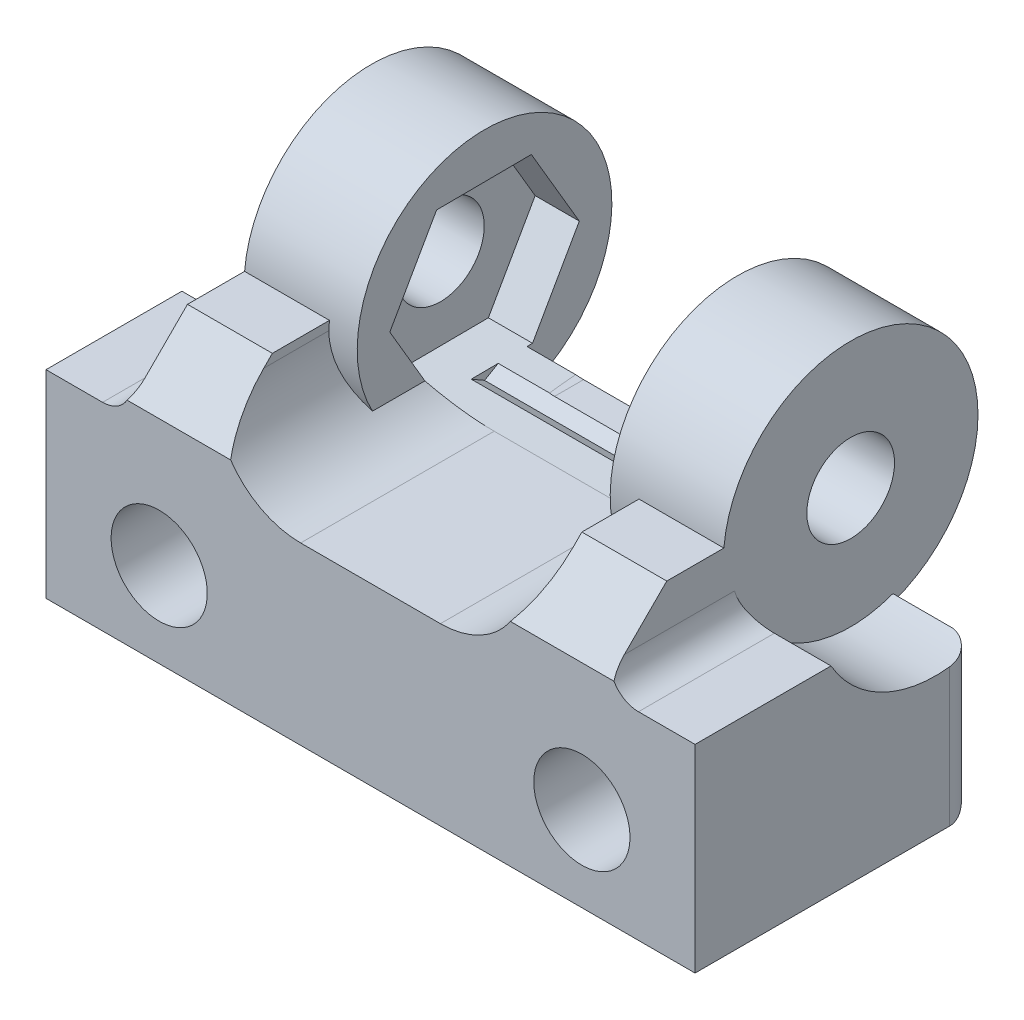
SolidWorks part; units mm, degrees
ref_plane "Спереди" through (0, 0, 0) normal (0, 0, 1) x (1, 0, 0)
ref_plane "Сверху" through (0, 0, 0) normal (0, 1, 0) x (1, 0, 0)
ref_plane "Справа" through (0, 0, 0) normal (1, 0, 0) x (0, 0, -1)
sketch "Эскиз1" plane through (0, 0, 0) normal (0, 0, 1) x (1, 0, 0)
  line L1 (-15, 4) -> (15, 4)
  line L2 (-15, 4) -> (-15, -4)
  line L3 (-15, -4) -> (15, -4)
  line L4 (15, 4) -> (15, -4)
  line L5 (-15, 4) -> (15, -4) construction
  line L6 (-15, -4) -> (15, 4) construction
  point P0 (0, 0)
  dimension "D1" = 30
  dimension "D2" = 8
extrude "Бобышка-Вытянуть1" add sketch "Эскиз1" along normal blind 5
sketch "Эскиз2" plane through (0, 0, 5) normal (0, 0, 1) x (1, 0, 0)
  line L0 (15, 4) -> (10.58, 4)
  line L1 (15, 4) -> (-15, 4) construction
  line L2 (10.58, 4) -> (-3.52, 4)
  line L3 (-3.52, 4) -> (-7.94, 4)
  line L4 (-7.94, 4) -> (-15, 4)
  line L5 (-15, 4) -> (-15, -4)
  line L6 (-15, 4) -> (-15, -4) construction
  line L7 (-15, -4) -> (-7.94, -4)
  line L8 (-15, -4) -> (15, -4) construction
  line L9 (-7.94, -4) -> (-7.94, 4)
  line M5 (15, 4) -> (-15, 4)
  line M6 (-15, 4) -> (-15, -4)
  line M7 (-15, -4) -> (15, -4)
  dimension "D1" = 4.42
  dimension "D2" = 14.1
  dimension "D3" = 4.42
extrude "Вырез-Вытянуть4" cut sketch "Эскиз2" against normal through all contours L9 M7 M5 M6 region at (-11.47, 0, 5)
sketch "Эскиз9" plane through (0, 0, 5) normal (0, 0, 1) x (1, 0, 0)
  line L0 (15, -4) -> (15, -1)
  line L1 (15, -4) -> (15, 4) construction
  line L2 (15, -1) -> (11, -1)
  line L3 (3.53, 4) -> (3.53, -4)
  line L4 (15, 4) -> (-7.94, 4) construction
  line L5 (-7.94, -4) -> (15, -4) construction
  circle A0 centre (11, -1) radius 1.5
  circle A1 centre (-3.94, -1) radius 1.5
  dimension "D3" = 3
  dimension "D1" = 3
  dimension "D2" = 4
extrude "Вырез-Вытянуть5" cut sketch "Эскиз9" against normal through all contours A1 | A0 region at (9.5424, -1, 5) region at (-3.94, -1, 5)
sketch "Эскиз10" plane through (0, 4, 0) normal (0, 1, 0) x (1, 0, 0)
  line L1 (-7.94, 0) -> (15, 0)
  line L2 (-7.94, 0) -> (-7.94, -5)
  line L3 (-7.94, -5) -> (15, -5)
  line L4 (15, 0) -> (15, -5)
extrude "Бобышка-Вытянуть2" add sketch "Эскиз10" along normal blind 4
sketch "Эскиз12" plane through (0, 0, 5) normal (0, 0, 1) x (1, 0, 0)
  line L0 (15, 8) -> (9, 8)
  line L1 (-7.94, 8) -> (15, 8) construction
  line L2 (9, 8) -> (-1.94, 8)
  line L3 (-1.94, 8) -> (-7.94, 8)
  line L4 (-1.94, 8) -> (-1.94, 2.1953)
  line L5 (-1.94, 2.1953) -> (9, 2.1953)
  line L6 (9, 2.1953) -> (9, 8)
  line M8 (15, 8) -> (-7.94, 8)
  dimension "D1" = 6
extrude "Вырез-Вытянуть6" cut sketch "Эскиз12" against normal through all contours L5 L6 L4 M8 region at (3.53, 5.0977, 5)
sketch "Эскиз14" plane through (9, 0, 0) normal (-1, 0, 0) x (0, 0, 1)
  line L0 (0, 8) -> (5, 2.1953)
  line L1 (5, 2.1953) -> (5, 8)
  line L2 (5, 8) -> (0, 2.1953)
  circle A0 centre (2.5, 5.0977) radius 1
  dimension "D1" = 2
extrude "Вырез-Вытянуть7" cut sketch "Эскиз14" against normal through all and the other way through all contours L0 A0 L2 | L0 A0 L2 | L2 A0 L0 | L2 A0 L0 region at (9, 5.7096, 2.5) region at (9, 5.0977, 1.9125) region at (9, 5.0977, 3.0875) region at (9, 4.4858, 2.5)
sketch "Эскиз15" plane through (9, 0, 0) normal (-1, 0, 0) x (0, 0, 1)
  line L1 (2.5, 2.7305) -> (4.55, 3.9141)
  line L2 (4.55, 3.9141) -> (4.55, 6.2812)
  line L3 (4.55, 6.2812) -> (2.5, 7.4648)
  line L4 (2.5, 7.4648) -> (0.45, 6.2812)
  line L5 (0.45, 6.2812) -> (0.45, 3.9141)
  line L6 (0.45, 3.9141) -> (2.5, 2.7305)
  circle A0 centre (2.5, 5.0977) radius 1
  circle A1 centre (2.5, 5.0977) radius 2.05 construction
  dimension "D1" = 4.1
extrude "Вырез-Вытянуть8" cut sketch "Эскиз15" against normal blind 1.7 and the other way blind 12.7
fillet "Скругление3" radius 3 2 edges at (-1.94, 2.1953, 2.5) (9, 2.1953, 2.5)
sketch "Эскиз17" plane through (15, 0, 0) normal (1, 0, 0) x (0, 0, -1)
  line L0 (-5, 8) -> (0, 8)
  line L1 (0, 8) -> (0, 3)
  line L2 (0, -4) -> (0, 8) construction
  line L3 (-5, 3) -> (-5, 8)
  line L4 (-5, -4) -> (-5, 8) construction
  line L5 (-5, 8) -> (-5.0493, 7.8026)
  line L6 (-4, 2) -> (-1, 2)
  arc A0 (-5, 3) -> (-4, 2) centre (-4, 3) ccw
  arc A1 (-1, 2) -> (0, 3) centre (-1, 3) ccw
  point P13 (-5, 2)
  point P16 (0, 2)
  circle M3 centre (-2.5, 5.0977) radius 1
  line M4 (0, -4) -> (0, 8)
  line M5 (0, 8) -> (-5, 8)
  line M6 (-5, 8) -> (-5, -4)
  dimension "D2" = 1
  dimension "D3" = 1
  dimension "D1" = 6
extrude "Вырез-Вытянуть10" cut sketch "Эскиз17" against normal blind 3 contours L6 A1 A0 M4 M5 M6 M3 region at (15, 7.9219, 2.5)
sketch "Эскиз18" plane through (-7.94, 0, 0) normal (-1, 0, 0) x (0, 0, 1)
  line L0 (0, 8) -> (5, 8)
  line L1 (5, 8) -> (5, 3)
  line L2 (5, -4) -> (5, 8) construction
  line L3 (4, 2) -> (1, 2)
  line L4 (0, -4) -> (0, 8) construction
  line L5 (0, 3) -> (0, 8)
  arc A0 (4, 2) -> (5, 3) centre (4, 3) ccw
  arc A1 (1, 2) -> (0, 3) centre (1, 3) cw
  point P12 (5, 2)
  point P15 (0, 2)
  dimension "D2" = 1
  dimension "D1" = 6
extrude "Вырез-Вытянуть11" cut sketch "Эскиз18" against normal blind 3
fillet "Скругление4" 2 edges at (-3.44, 8, 0) (-3.44, 8, 5) type full round first side face at (-2.44, -1, 0) second side face at (12.5, -1, 5) middle face at (-3.44, 8, 2.5)
fillet "Скругление5" 2 edges at (10.5, 8, 5) (10.5, 8, 0) type full round first side face at (12.5, -1, 5) second side face at (-2.44, -1, 0) middle face at (10.5, 8, 2.5)
sketch "Эскиз19" plane through (0, 0, 0) normal (0, 0, -1) x (-1, 0, 0)
  line L0 (-15, -4) -> (-15, 3)
  line L1 (-15, 3) -> (7.94, 3)
  line L2 (7.94, 3) -> (7.94, -4)
  line L3 (7.94, -4) -> (-15, -4)
extrude "Вырез-Вытянуть12" cut sketch "Эскиз19" against normal blind 1
fillet "Скругление6" radius 3 2 edges at (10.0223, 3, 0) (-2.9623, 3, 0)
fillet "Скругление7" radius 1 5 edges at (-6.44, 2, 1) (13.5, 2, 1) (15, -1, 1) (3.53, -4, 1) (-7.94, -1, 1)
sketch "Эскиз20" plane through (0, 0, 5) normal (0, 0, 1) x (1, 0, 0)
  line L0 (12, 3) -> (15, 3)
  line L1 (15, 3) -> (15, -4)
  line L2 (15, -4) -> (-7.94, -4)
  line L3 (-7.94, -4) -> (-7.94, 3)
  line L4 (-7.94, 3) -> (-4.94, 3)
  line L5 (-4.94, 3) -> (-4.94, 5.5)
  line L6 (-4.94, 5.5) -> (-1.94, 5.5)
  line L7 (12, 3) -> (12, 5.5)
  line L8 (12, 5.5) -> (9, 5.5)
  line L9 (6, 2.1953) -> (1.06, 2.1953)
  line L10 (1.06, 2.1953) -> (1.06, 5.5)
  line L11 (1.06, 5.5) -> (-1.94, 5.5)
  line L12 (6, 2.1953) -> (6, 5.5)
  line L13 (6, 5.5) -> (9, 5.5)
  circle A2 centre (11, -1) radius 1.5
  circle A3 centre (-3.94, -1) radius 1.5
extrude "Бобышка-Вытянуть4" add sketch "Эскиз20" along normal blind 6
sketch "Эскиз23" plane through (0, 0, 5) normal (0, 0, -1) x (-1, 0, 0)
  line L0 (-6, 5.5) -> (-9, 5.5)
  line L1 (-6, 5.5) -> (-6, 2.1953)
  line L2 (-1.06, 2.1953) -> (-1.06, 5.5)
  line L3 (-1.06, 5.5) -> (1.94, 5.5)
  line L4 (-9, 5.5) -> (-9, 2.1953)
  line L5 (-9, 2.1953) -> (-6, 2.1953)
  line L6 (-9, 5.1953) -> (1.94, 5.1953)
  line L7 (1.94, 5.5) -> (1.94, 5.1953)
  arc A0 (-9, 5.1953) -> (-6, 2.1953) centre (-6, 5.1953) ccw
  arc A1 (1.94, 5.1953) -> (-1.06, 2.1953) centre (-1.06, 5.1953) cw
  line M2 (-6, 5.5) -> (-9, 5.5)
  line M3 (-9, 5.5) -> (-9, 5.1953)
  arc M4 (-9, 5.1953) -> (-6, 2.1953) centre (-6, 5.1953) ccw
  line M5 (-6, 2.1953) -> (-6, 5.5)
extrude "Вырез-Вытянуть13" cut sketch "Эскиз23" against normal blind 6 contours L6 M4 M5 | L6 L1 M3 M2 | A1 L6 L2 | L7 L3 L2 L6 region at (7.5, 5.3477, 5) region at (-0.44, 5.3477, 5) region at (-0.2132, 3.9221, 5) region at (7.2732, 3.9221, 5)
chamfer "Фаска1" distance 2 angle 45 2 edges at (-3.44, 5.5, 11) (10.5, 5.5, 11)
fillet "Скругление8" radius 1 1 edges at (12, 3, 8)
fillet "Скругление9" radius 1 1 edges at (-4.94, 3, 8)
sketch "Эскиз24" plane through (0, 0, 11) normal (0, 0, 1) x (1, 0, 0)
  line L0 (-3.94, -1) -> (11, -1)
  line L1 (1.06, 2.1953) -> (1.06, -1)
  line L2 (-3.94, -1) -> (-7.94, -1)
  line L3 (-7.94, 3) -> (-7.94, -4) construction
sketch "Эскиз25" plane through (-4.94, 0, 0) normal (-1, 0, 0) x (0, 0, 1)
  circle A0 centre (2.5, 5.0977) radius 1.55
  dimension "D1" = 3.1
extrude "Вырез-Вытянуть14" cut sketch "Эскиз25" against normal through all
sketch "Эскиз26" plane through (9, 0, 0) normal (-1, 0, 0) x (0, 0, 1)
  line L2 (2.5, 1.9222) -> (5.25, 3.51)
  line L3 (5.25, 3.51) -> (5.25, 6.6854)
  line L4 (5.25, 6.6854) -> (2.5, 8.2731)
  line L5 (2.5, 8.2731) -> (-0.25, 6.6854)
  line L6 (-0.25, 6.6854) -> (-0.25, 3.51)
  line L7 (-0.25, 3.51) -> (2.5, 1.9222)
  circle A0 centre (2.5, 5.0977) radius 2.75 construction
  dimension "D1" = 5.5
sketch "Эскиз27" plane through (-4.94, 0, 0) normal (-1, 0, 0) x (0, 0, 1)
  circle A0 centre (2.5, 5.0977) radius 1.55
  circle A1 centre (2.5, 5.0977) radius 4
  dimension "D1" = 3.1
  dimension "D2" = 8
extrude "Бобышка-Вытянуть5" add sketch "Эскиз27" against normal blind 4
sketch "Эскиз28" plane through (12, 0, 0) normal (1, 0, 0) x (0, 0, -1)
  circle A0 centre (-2.5, 5.0977) radius 1.55
  circle A1 centre (-2.5, 5.0977) radius 4
  dimension "D1" = 3.1
  dimension "D2" = 8
extrude "Бобышка-Вытянуть6" add sketch "Эскиз28" against normal blind 4
sketch "Эскиз29" plane through (-4.94, 0, 0) normal (-1, 0, 0) x (0, 0, 1)
  circle A0 centre (2.5, 5.0977) radius 4
  dimension "D1" = 8
extrude "Вырез-Вытянуть15" cut sketch "Эскиз29" along normal blind 4
sketch "Эскиз30" plane through (12, 0, 0) normal (1, 0, 0) x (0, 0, -1)
  circle A0 centre (-2.5, 5.0977) radius 4
  dimension "D1" = 8
extrude "Вырез-Вытянуть16" cut sketch "Эскиз30" along normal blind 4
extrude "Вырез-Вытянуть17" cut sketch "Эскиз26" against normal blind 0.5 and the other way blind 11.5
sketch "Эскиз31" plane through (-4.94, 0, 0) normal (-1, 0, 0) x (0, 0, 1)
  circle A0 centre (2.5, 5.0977) radius 4.25
  dimension "D1" = 8.5
extrude "Вырез-Вытянуть18" cut sketch "Эскиз31" along normal blind 3
sketch "Эскиз32" plane through (12, 0, 0) normal (1, 0, 0) x (0, 0, -1)
  circle A0 centre (-2.5, 5.0977) radius 4.25
  dimension "D1" = 8.5
extrude "Вырез-Вытянуть19" cut sketch "Эскиз32" along normal blind 3
sketch "Эскиз33" plane through (0, 0, 1) normal (0, 0, -1) x (-1, 0, 0)
  circle A0 centre (-11, -1) radius 1.7
  circle A1 centre (3.94, -1) radius 1.7
  dimension "D1" = 3.4
extrude "Вырез-Вытянуть20" cut sketch "Эскиз33" against normal through all
sketch "Эскиз34" plane through (-4.94, 0, 0) normal (-1, 0, 0) x (0, 0, 1)
  circle A0 centre (2.5, 5.0977) radius 4.5
  circle A1 centre (2.5, 5.0977) radius 1.7
  dimension "D1" = 9
  dimension "D2" = 3.4
extrude "Бобышка-Вытянуть7" add sketch "Эскиз34" against normal up to surface (4 mm away) up to face at (-0.94, 5.0546, 2.5013)
sketch "Эскиз35" plane through (12, 0, 0) normal (1, 0, 0) x (0, 0, -1)
  circle A0 centre (-2.5, 5.0977) radius 4.5
  circle A1 centre (-2.5, 5.0977) radius 1.75
  dimension "D1" = 3.5
extrude "Бобышка-Вытянуть8" add sketch "Эскиз35" against normal up to surface (4 mm away) up to face at (8, 5.0546, 2.5013)
sketch "Эскиз37" plane through (-0.94, 0, 0) normal (1, 0, 0) x (0, 0, -1)
  line L1 (-0.8467, 8.0097) -> (-4.1952, 7.9855)
  line L2 (-4.1952, 7.9855) -> (-5.8485, 5.0735)
  line L3 (-5.8485, 5.0735) -> (-4.1533, 2.1857)
  line L4 (-4.1533, 2.1857) -> (-0.8048, 2.2098)
  line L5 (-0.8048, 2.2098) -> (0.8485, 5.1218)
  line L6 (0.8485, 5.1218) -> (-0.8467, 8.0097)
  circle A0 centre (-2.5, 5.0977) radius 2.9 construction
  dimension "D1" = 5.8
extrude "Вырез-Вытянуть21" cut sketch "Эскиз37" against normal up to surface and the other way up to surface up to face at (-2.5, 5.0977, 4.05) other way up to face at (9.5, 5.0977, 4.05)
